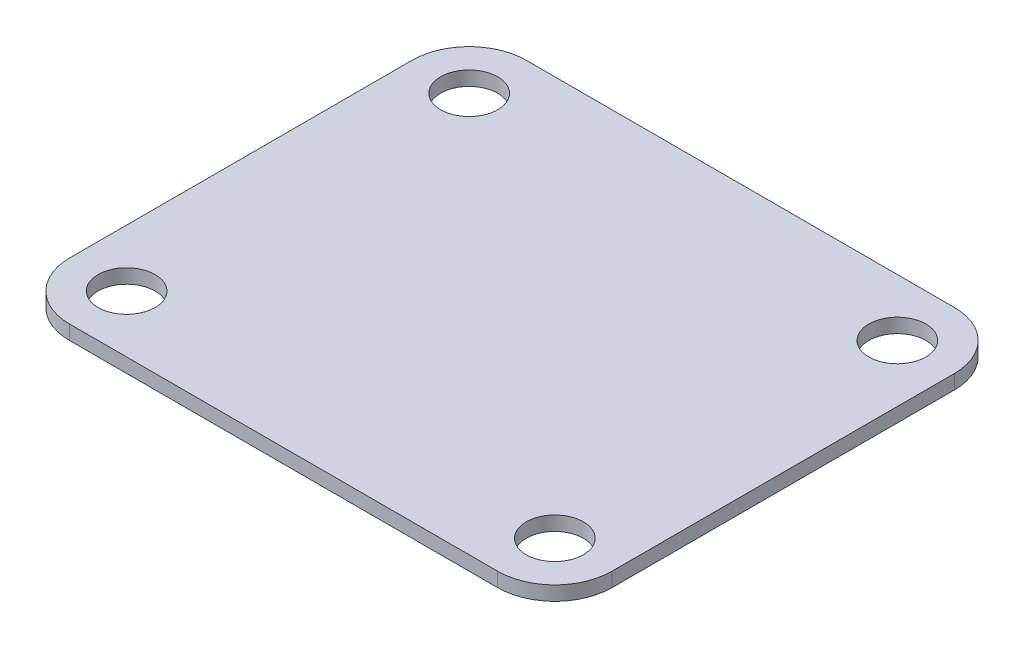
SolidWorks part; units mm, degrees
ref_plane "Front Plane" through (0, 0, 0) normal (0, 0, 1) x (1, 0, 0)
ref_plane "Top Plane" through (0, 0, 0) normal (0, 1, 0) x (1, 0, 0)
ref_plane "Right Plane" through (0, 0, 0) normal (1, 0, 0) x (0, 0, -1)
sketch "Sketch2" plane through (0, 0, 0) normal (0, 1, 0) x (1, 0, 0)
  line L0 (0, 0) -> (0, 20.6431) construction
  line L1 (19, -16) -> (-19, -16)
  line L2 (19, -16) -> (19, 16)
  line L3 (19, 16) -> (-19, 16)
  line L4 (-19, -16) -> (-19, 16)
  line L5 (19, -16) -> (-19, 16) construction
  line L6 (19, 16) -> (-19, -16) construction
  line L7 (0, 0) -> (-36.8648, 0) construction
  circle A1 centre (-15, 12) radius 2
  circle A2 centre (15, 12) radius 2
  circle A3 centre (15, -12) radius 2
  circle A4 centre (-15, -12) radius 2
  point P0 (0, 0)
  dimension "D3" = 12
  dimension "D4" = 15
  dimension "D1" = 38
  dimension "D2" = 32
extrude "Boss-Extrude1" add sketch "Sketch2" along normal blind 1
fillet "Fillet1" radius 4 4 edges at (-19, 0.5, -16) (19, 0.5, -16) (19, 0.5, 16) (-19, 0.5, 16)
sketch "Sketch3" plane through (0, 0, 0) normal (0, -1, 0) x (1, 0, 0)
  circle A0 centre (0, 0) radius 13
  dimension "D1" = 26
extrude "Boss-Extrude2" add sketch "Sketch3" along normal blind 3
sketch "Sketch4" plane through (0, -3, 0) normal (0, -1, 0) x (1, 0, 0)
  circle A0 centre (0, 0) radius 12
  dimension "D1" = 24
extrude "Cut-Extrude1" cut sketch "Sketch4" against normal blind 2
fillet "Fillet2" radius 2 1 edges at (0, 0, -13)
sketch "Sketch5" plane through (0, -1, 0) normal (0, -1, 0) x (1, 0, 0)
  circle A0 centre (0, 0) radius 6
sketch "Sketch7" plane through (0, -3, 0) normal (0, -1, 0) x (1, 0, 0)
  line L0 (0, 0) -> (-37.412, 0) construction
  line L9 (12.2107, -4.4609) -> (18.1726, -4.4609)
  circle A0 centre (0, 0) radius 12 construction
  circle A1 centre (0, 0) radius 13 construction
  circle A2 centre (0, 0) radius 12
  circle A3 centre (0, 0) radius 13
extrude "Cut-Extrude4" cut sketch "Sketch5" against normal blind 1 contours A0
sketch "Sketch11" plane through (0, 0, 0) normal (0, -1, 0) x (1, 0, 0)
  circle A0 centre (0, 0) radius 5
extrude "Boss-Extrude5" add sketch "Sketch11" along normal blind 2
fillet "Fillet7" radius 1 3 edges at (0, -1, -12) (0, -2, -5) (0, -1, -6)
